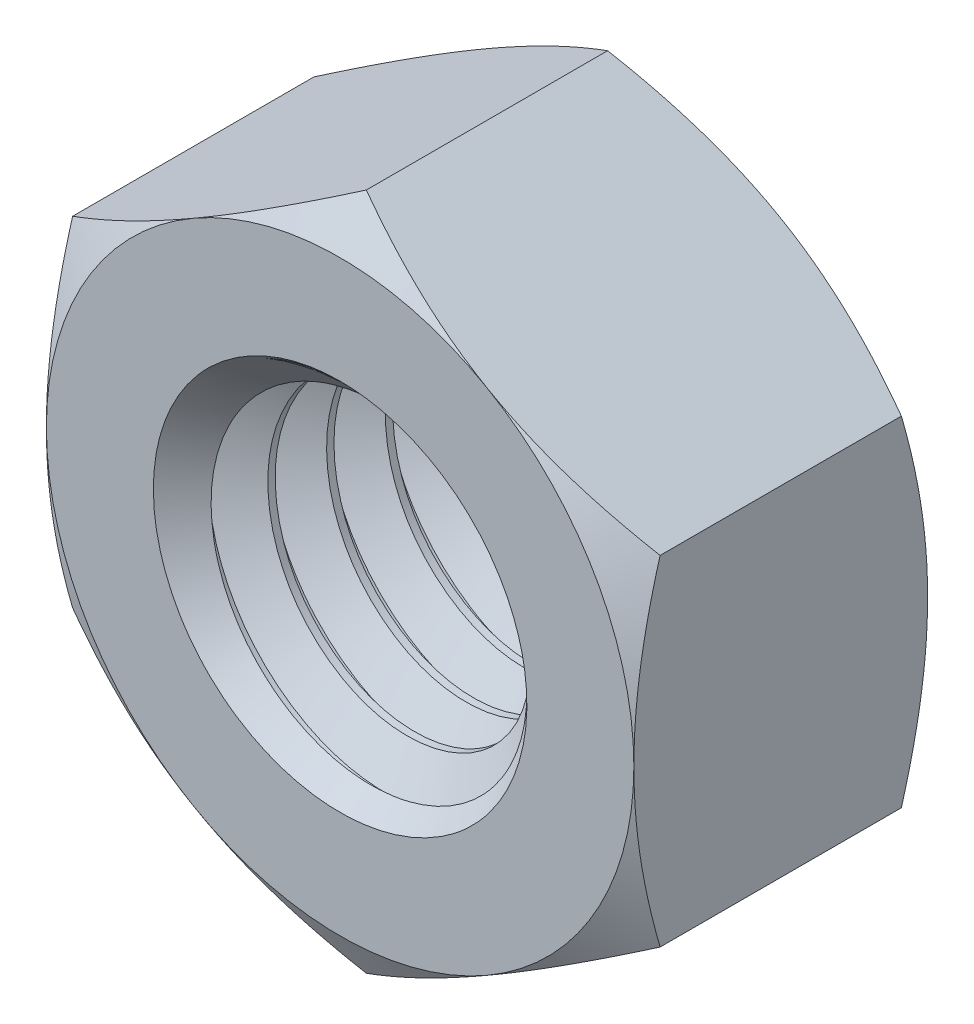
SolidWorks part; units mm, degrees
ref_plane "Front Plane" through (0, 0, 0) normal (0, 0, 1) x (1, 0, 0)
ref_plane "Top Plane" through (0, 0, 0) normal (0, 1, 0) x (1, 0, 0)
ref_plane "Right Plane" through (0, 0, 0) normal (1, 0, 0) x (0, 0, -1)
sketch "Sketch1" plane through (0, 0, 0) normal (1, 0, 0) x (0, 0, -1)
  line L0 (-2, 0) -> (2, 0) construction
  line L1 (-2, -4) -> (-2, 4) construction
  line L2 (2, -4) -> (2, 4) construction
  line L3 (-2, -2.5) -> (-2, 2.5) construction
  line L4 (-2.75, 2.5866) -> (-2.35, 1.8938) construction
  line L5 (-2.35, 1.8938) -> (-1.95, 2.5866) construction
  line L6 (-1.95, 2.5866) -> (-2.75, 2.5866) construction
  line L7 (-2.725, 2.5433) -> (-1.975, 2.5433) construction
  line L8 (-2.7, 2.5) -> (-2, 2.5) construction
  line L9 (-2.4, 1.9804) -> (-2.3, 1.9804) construction
  line L10 (-2.35, 1.9804) -> (-2.35, 1.8938) construction
  line L11 (-2.35, 2.5866) -> (-2.35, 2.5) construction
  point P4 (0, 0)
  point P7 (-2, 0)
  point P11 (2, 0)
  point P14 (-2, 0)
  point P26 (-2.35, 2.5433)
  point P27 (-2, -2.5)
  dimension "Height" = 4
  dimension "Width" = 8
  dimension "Thread OD" = 5
  dimension "D1" = 60
  dimension "Pitch" = 0.8
  dimension "D2" = 0.1
sketch "Sketch2" plane through (0, 0, 0) normal (0, 0, 1) x (1, 0, 0)
  line L1 (0, 4.6188) -> (-4, 2.3094)
  line L2 (-4, 2.3094) -> (-4, -2.3094)
  line L3 (-4, -2.3094) -> (0, -4.6188)
  line L4 (0, -4.6188) -> (4, -2.3094)
  line L5 (4, -2.3094) -> (4, 2.3094)
  line L6 (4, 2.3094) -> (0, 4.6188)
  circle A0 centre (0, 0) radius 4 construction
  circle A1 centre (0, 0) radius 2.5
extrude "Boss-Extrude1" add sketch "Sketch2" along normal up to vertex (2 mm away) and the other way up to vertex (2 mm away) up to point (0, -4, 2) other way up to point (0, -4, -2)
sketch "Sketch3" plane through (0, 0, 2) normal (0, 0, 1) x (1, 0, 0)
  circle A0 centre (0, 0) radius 4
extrude "Cut-Extrude1" cut sketch "Sketch3" against normal through all draft 60 flip side to cut
mirror "Mirror1" about plane through (0, 0, 0) normal (0, 0, 1) of "Cut-Extrude1"
ref_axis "Center Axis 1" through (0, 0, -10.9016) along (0, 0, 1)
ref_plane "Contact Plane 1" through (0, 0, 2) normal (0, 0, 1) x (1, 0, 0)
ref_plane "Contact Plane 2" through (0, 0, -2) normal (0, 0, -1) x (-1, 0, 0)
sketch "Sketch4" plane through (0, 0, 0) normal (1, 0, 0) x (0, 0, -1)
  line L1 (-2.725, 2.5433) -> (-2.4, 1.9804)
  line L2 (-2.4, 1.9804) -> (-2.3, 1.9804)
  line L3 (-2.3, 1.9804) -> (-1.975, 2.5433)
  line L4 (-2.725, 2.5433) -> (-1.975, 2.5433) construction
  line L5 (-2.725, 2.5433) -> (-1.975, 2.5433)
sketch "Sketch5" plane through (0, 0, 2) normal (0, 0, 1) x (1, 0, 0)
  circle A0 centre (0, 0) radius 2.5 construction
  circle A1 centre (0, 0) radius 2.5
curve "Helix/Spiral1" pitch 0.8 height 4.8 radius 2.5 centre (0, 0, 2) axis (0, 0, -1) start towards (0, 1, 0)
sweep "Sweep1" add profiles "Sketch4" path "Helix/Spiral1"
sketch "Sketch6" plane through (0, 0, 2) normal (0, 0, 1) x (1, 0, 0)
  circle A1 centre (0, 0) radius 2.5433
extrude "Cut-Extrude2" cut sketch "Sketch6" along normal through all and the other way through all draft 45
sketch "Sketch7" plane through (0, 0, -2) normal (0, 0, -1) x (-1, 0, 0)
  circle A1 centre (0, 0) radius 2.5433
  circle A2 centre (0, 0) radius 2.5433
  dimension "D1" = 0
extrude "Cut-Extrude3" cut sketch "Sketch7" along normal through all and the other way through all draft 45
equation "\"D2@Sketch1\"=\"Pitch@Sketch1\"/8"
equation "\"D4@Helix/Spiral1\"=\"Pitch@Sketch1\""
equation "\"D3@Helix/Spiral1\"=\"Height@Sketch1\"+\"Pitch@Sketch1\""
